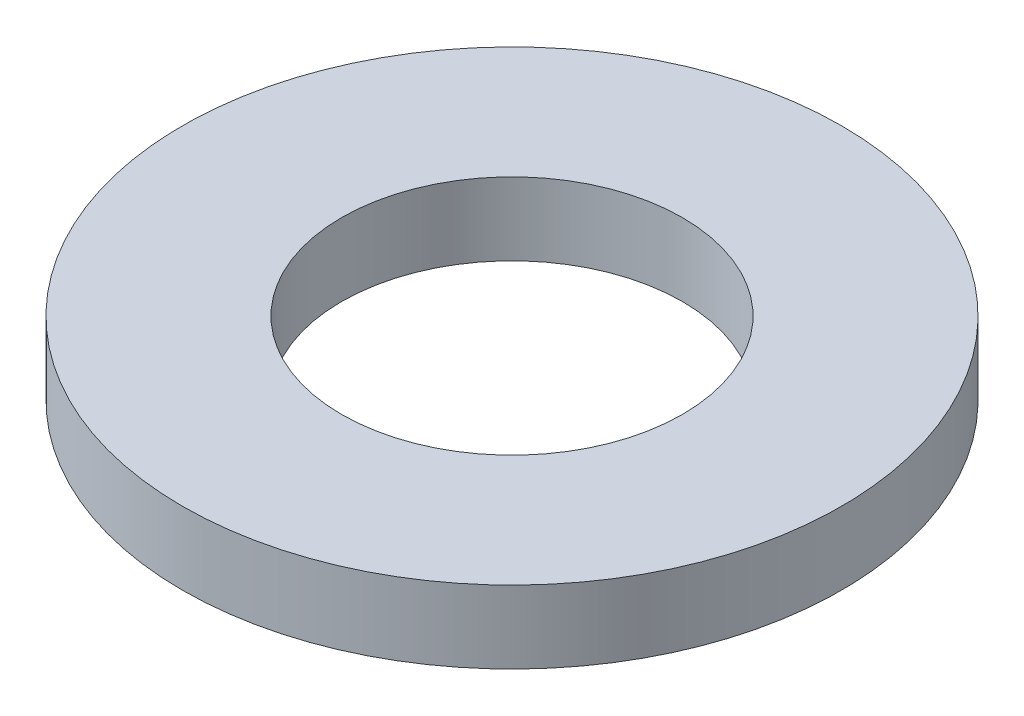
SolidWorks part; units mm, degrees
ref_plane "Front Plane" through (0, 0, 0) normal (0, 0, 1) x (1, 0, 0)
ref_plane "Top Plane" through (0, 0, 0) normal (0, 1, 0) x (1, 0, 0)
ref_plane "Right Plane" through (0, 0, 0) normal (1, 0, 0) x (0, 0, -1)
sketch "Sketch1" plane through (0, 0, 0) normal (0, 1, 0) x (1, 0, 0)
  circle A0 centre (0, 0) radius 72.5
  dimension "FLANGE_OD" = 145
extrude "Boss-Extrude1" add sketch "Sketch1" along normal blind 16
sketch "Sketch2" plane through (0, 0, 0) normal (0, 1, 0) x (1, 0, 0)
  circle A0 centre (0, 0) radius 37.5
  dimension "BORE_D" = 75
extrude "Cut-Extrude1" cut sketch "Sketch2" along normal through all
sketch "Sketch3" plane through (0, 16, 0) normal (0, 1, 0) x (1, 0, 0)
  circle A0 centre (0, 0) radius 21.8364 construction
  circle A1 centre (-21.8364, 0) radius 4.2953
  dimension "BOLT_D" = 8.5905
  dimension "BOLT_PCD" = 43.6728
extrude "Cut-Extrude2" cut sketch "Sketch3" against normal blind 9.7199 rebuild error yes
pattern_circular "CirPattern1" count 5 over 360 rebuild error yes
